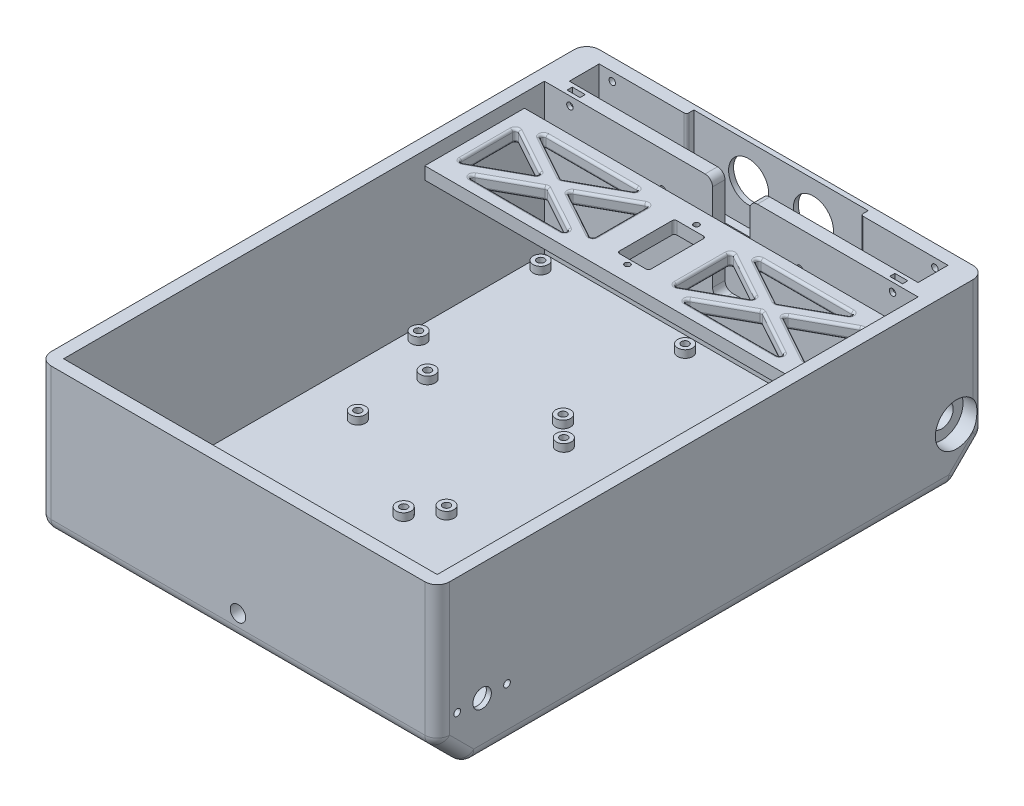
SolidWorks part; units mm, degrees
ref_plane "Front Plane" through (0, 0, 0) normal (0, 0, 1) x (1, 0, 0)
ref_plane "Top Plane" through (0, 0, 0) normal (0, 1, 0) x (1, 0, 0)
ref_plane "Right Plane" through (0, 0, 0) normal (1, 0, 0) x (0, 0, -1)
sketch "Main Body" plane through (0, 0, 0) normal (0, 1, 0) x (1, 0, 0)
  line L0 (-75, 110) -> (75, 110)
  line L1 (-75, -105) -> (75, -105)
  line L2 (-75, -105) -> (-75, 105)
  line L3 (-75, 105) -> (75, 105)
  line L4 (75, -105) -> (75, 105)
  line L5 (-75, -105) -> (75, 105) construction
  line L6 (-75, 105) -> (75, -105) construction
  line L7 (80, -105) -> (80, 105)
  line L8 (-75, -110) -> (75, -110)
  line L9 (-80, -105) -> (-80, 105)
  line L10 (-80, -110) -> (80, -110) construction
  line L11 (-80, -110) -> (-80, 110) construction
  line L12 (80, -110) -> (80, 110) construction
  line L13 (-80, 110) -> (80, 110) construction
  arc A0 (-75, -110) -> (-80, -105) centre (-75, -105) cw
  arc A1 (80, -105) -> (75, -110) centre (75, -105) cw
  arc A2 (75, 110) -> (80, 105) centre (75, 105) cw
  arc A3 (-75, 110) -> (-80, 105) centre (-75, 105) ccw
  point P0 (0, 0)
  dimension "D4" = 5
  dimension "D1" = 75
  dimension "D2" = 210
  dimension "D3" = 5
extrude "Boss-Extrude1" add sketch "Main Body" along normal blind 8 contours L1 L4 L3 L2 | L9 L8 L7 L0 L4 L1 L2 L3 region at (0, 0, -107.2797) region at (0, 0, 0)
extrude "Boss-Extrude3" add sketch "Main Body<4>" along normal blind 60 from surface starting at face at (0, 8, 0)
sketch "Main Body<4>" plane through (0, 0, 0) normal (0, 1, 0) x (1, 0, 0) same geometry as "Main Body"
sketch "Sketch1" plane through (75, 0, 0) normal (-1, 0, 0) x (0, 0, 1)
  line L0 (105, 68) -> (105, 8) construction
  line L1 (-105, 8) -> (105, 8) construction
  line L2 (79, 15.5) -> (105, 15.5)
  line L3 (79, 8) -> (105, 8)
  line L4 (79, 8) -> (79, 34)
  line L5 (79, 34) -> (105, 34)
  line L6 (105, 8) -> (105, 34)
  line L7 (79, 8) -> (105, 34) construction
  line L8 (79, 34) -> (105, 8) construction
  circle A0 centre (92, 21) radius 13
  line M2 (-105, 8) -> (105, 8)
  line M3 (105, 8) -> (105, 68)
  dimension "D1" = 26
  dimension "D2" = 7.5
extrude "Boss-Extrude4" add sketch "Sketch1" along normal up to surface (150 mm away) contours A0 L4 M2 | A0 L3 M3 region at (75, 10.5201, 82.0674) region at (75, 10.5201, 101.9326) up to face at (-75, 38, 0)
sketch "Sketch2" plane through (0, 0, 0) normal (1, 0, 0) x (0, 0, -1)
  line L0 (-105, 68) -> (-105, 15.5) construction
  line L1 (-105, 8) -> (-79, 8)
  line L2 (-105, 8) -> (-105, 15.5)
  line L3 (-105, 15.5) -> (-79, 15.5)
  line L4 (-79, 8) -> (-79, 15.5)
  line L5 (105, 8) -> (-79, 8) construction
  line L6 (-79, 8) -> (-79, 15.5) construction
  line L7 (-79, 15.5) -> (-80.2208, 15.5) construction
extrude "Cut-Extrude1" cut sketch "Sketch2" against normal mid plane 12
sketch "Sketch3" plane through (0, 8, 0) normal (0, 1, 0) x (1, 0, 0)
  line L0 (75, -105) -> (-75, -105) construction
  line L1 (-4, -79) -> (-11, -79)
  line L2 (-4, -79) -> (-4, -105)
  line L3 (-4, -105) -> (-11, -105)
  line L4 (-11, -79) -> (-11, -105)
  line L5 (0, 0) -> (0, -105) construction
  line L6 (-75, -79) -> (-6, -79) construction
  line L7 (11, -79) -> (11, -105)
  line L8 (4, -105) -> (11, -105)
  line L9 (4, -79) -> (4, -105)
  line L10 (4, -79) -> (11, -79)
  line L11 (-6, -103.7792) -> (-6, -92) construction
  dimension "D1" = 5
  dimension "D2" = 4
extrude "Boss-Extrude5" add sketch "Sketch3" along normal blind 20
sketch "Sketch4" plane through (0, 8, 0) normal (0, 1, 0) x (1, 0, 0)
  line L0 (-75, -105) -> (-75, 105) construction
  line L1 (-75, 93) -> (75, 93)
  line L2 (-75, 93) -> (-75, 88)
  line L3 (-75, 88) -> (75, 88)
  line L4 (75, 93) -> (75, 88)
  line L5 (75, 105) -> (75, -105) construction
  line L6 (-75, 105) -> (75, 105) construction
  dimension "D1" = 17
  dimension "D2" = 5
extrude "Boss-Extrude6" add sketch "Sketch4" along normal up to surface (60 mm away) up to face at (0, 68, 0)
sketch "Sketch5" plane through (80, 0, 0) normal (1, 0, 0) x (0, 0, -1)
  circle A0 centre (-92, 21) radius 3.5 construction
  circle A1 centre (-92, 21) radius 3.5
  circle A2 centre (-92, 21) radius 3.7
  dimension "D1" = 0.2
extrude "Cut-Extrude4" cut sketch "Sketch5" against normal up to next contours A1 | A2 A1 region at (80, 21, 92) region at (80, 21, 95.5953)
sketch "Sketch6" plane through (-75, 0, 0) normal (1, 0, 0) x (0, 0, -1)
  circle A0 centre (-92, 21) radius 13
  dimension "D1" = 26
extrude "Cut-Extrude5" cut sketch "Sketch6" against normal offset from surface (3 mm away) 2 up to face at (-80, 34, 0)
mirror "Mirror1" about plane through (0, 0, 0) normal (1, 0, 0) of "Cut-Extrude4"
sketch "Sketch8" plane through (75, 0, 0) normal (-1, 0, 0) x (0, 0, 1)
  circle A0 centre (92, 21) radius 13
  dimension "D1" = 26
extrude "Cut-Extrude6" cut sketch "Sketch8" against normal offset from surface (3 mm away) 2 up to face at (80, 21, 88.3)
sketch "Sketch10" plane through (80, 0, 0) normal (1, 0, 0) x (0, 0, -1)
  circle A1 centre (-82, 21) radius 1.25
  circle A2 centre (-82, 21) radius 1.25
  circle A3 centre (-102, 21) radius 1.25
  circle A4 centre (-102, 21) radius 1.25
  circle A5 centre (-92, 21) radius 12.5
  circle A6 centre (-92, 21) radius 12.5
  circle A63 centre (-102, 21) radius 1.35
  circle A64 centre (-82, 21) radius 1.35
  dimension "D1" = 0
  dimension "D2" = 0
  dimension "D3" = 0
  dimension "D4" = 0.1
  dimension "D5" = 0.1
extrude "Cut-Extrude7" cut sketch "Sketch10" against normal up to next contours A2 | A64 A2 | A4 | A63 A4 region at (80, 21, 82) region at (80, 21, 102) region at (80, 21, 103.3118) region at (80, 21, 83.3118)
mirror "Mirror3" about plane through (0, 0, 0) normal (1, 0, 0) of "Cut-Extrude7"
sketch "Sketch11" plane through (80, 0, 0) normal (1, 0, 0) x (0, 0, -1)
  circle A0 centre (98.5, 21) radius 4.5 construction
  circle A1 centre (98.5, 21) radius 4.5
  circle A3 centre (98.5, 21) radius 4.6
  dimension "D1" = 0.1
extrude "Cut-Extrude10" cut sketch "Sketch11" against normal through all contours A1 | A3 A1 region at (80, 21, -98.5) region at (80, 21, -93.913)
sketch "Sketch12" plane through (-75, 0, 0) normal (1, 0, 0) x (0, 0, -1)
  line L0 (93, 8) -> (105, 8) construction
  line L1 (93, 68) -> (105, 68)
  line L2 (93, 68) -> (93, 8)
  line L3 (93, 8) -> (105, 8)
  line L4 (105, 68) -> (105, 8)
  line L6 (93, 68) -> (93, 8) construction
  line L7 (93, 68) -> (105, 68) construction
  circle A2 centre (98.5, 21) radius 4.6 construction
  circle A3 centre (98.5, 21) radius 4.6
extrude "Boss-Extrude7" add sketch "Sketch12" along normal blind 5
sketch "Sketch13" plane through (-80, 0, 0) normal (-1, 0, 0) x (0, 0, 1)
  circle A0 centre (-98.5, 21) radius 8.55
  circle A2 centre (-98.5, 21) radius 4.6 construction
  dimension "D1" = 17.1
extrude "Cut-Extrude11" cut sketch "Sketch13" against normal blind 6
mirror "Mirror4" about plane through (0, 0, 0) normal (1, 0, 0) of "Boss-Extrude7", "Cut-Extrude11"
sketch "Sketch14" plane through (0, 8, 0) normal (0, 1, 0) x (1, 0, 0)
  line L0 (-4, -105) -> (-4, -79) construction
  line L1 (-4, -95) -> (4, -95)
  line L2 (-4, -95) -> (-4, -105)
  line L3 (-4, -105) -> (4, -105)
  line L4 (4, -95) -> (4, -105)
  dimension "D1" = 10
extrude "Boss-Extrude9" add sketch "Sketch14" along normal blind 5
sketch "Sketch15" plane through (0, 0, 110) normal (0, 0, 1) x (1, 0, 0)
  arc A0 (-3, 19.5) -> (3, 19.5) centre (0, 19.5) ccw construction
  arc A1 (-3, 19.5) -> (3, 19.5) centre (0, 19.5) ccw
  arc A2 (3, 19.5) -> (-3, 19.5) centre (0, 19.5) ccw construction
  arc A3 (3, 19.5) -> (-3, 19.5) centre (0, 19.5) ccw
  arc A4 (3.1, 19.5) -> (-3.1, 19.5) centre (0, 19.5) ccw
  arc A5 (-3.1, 19.5) -> (3.1, 19.5) centre (0, 19.5) ccw
  dimension "D1" = 0.1
extrude "Cut-Extrude12" cut sketch "Sketch15" against normal up to next contours A1 A3 | A4 A5 A3 A1 region at (0, 19.5, 110) region at (0, 16.4877, 110)
sketch "Sketch16" plane through (0, 0, 0) normal (0, -1, 0) x (1, 0, 0)
  circle A0 centre (-12.5, -82) radius 1.475 construction
  circle A1 centre (-70.5, -82) radius 1.475 construction
  circle A2 centre (-70.5, -33) radius 1.475 construction
  circle A3 centre (-12.5, -33) radius 1.475 construction
  circle A4 centre (-4.2, -25) radius 1.475 construction
  circle A5 centre (-55, -21.12) radius 1.475 construction
  circle A6 centre (-55, 6.88) radius 1.475 construction
  circle A7 centre (-4.2, 22.08) radius 1.475 construction
  circle A8 centre (-12.3, 31.18) radius 1.475 construction
  circle A9 centre (24.2, 31.18) radius 1.475 construction
  circle A10 centre (37.8459, 24.117) radius 1.475 construction
  circle A11 centre (59.5541, 24.117) radius 1.475 construction
  circle A12 centre (59.5541, 68.243) radius 1.475 construction
  circle A13 centre (37.8459, 68.243) radius 1.475 construction
  circle A14 centre (24.2, 67.68) radius 1.475 construction
  circle A15 centre (-12.3, 67.68) radius 1.475 construction
  circle A16 centre (-12.5, -82) radius 1.475
  circle A17 centre (-70.5, -82) radius 1.475
  circle A18 centre (-70.5, -33) radius 1.475
  circle A19 centre (-12.5, -33) radius 1.475
  circle A20 centre (-4.2, -25) radius 1.475
  circle A21 centre (-55, -21.12) radius 1.475
  circle A22 centre (-55, 6.88) radius 1.475
  circle A23 centre (-4.2, 22.08) radius 1.475
  circle A24 centre (-12.3, 31.18) radius 1.475
  circle A25 centre (24.2, 31.18) radius 1.475
  circle A26 centre (37.8459, 24.117) radius 1.475
  circle A27 centre (59.5541, 24.117) radius 1.475
  circle A28 centre (59.5541, 68.243) radius 1.475
  circle A29 centre (37.8459, 68.243) radius 1.475
  circle A30 centre (24.2, 67.68) radius 1.475
  circle A31 centre (-12.3, 67.68) radius 1.475
extrude "Cut-Extrude13" cut sketch "Sketch16" against normal up to next
sketch "Sketch17" plane through (0, 8, 0) normal (0, 1, 0) x (1, 0, 0)
  line L0 (0, 88) -> (0, -110) construction
  line L1 (-75, 88) -> (75, 88) construction
  line L2 (75, -110) -> (-75, -110) construction
  line L3 (-75, 4.5) -> (75, 4.5) construction
  line L7 (-75, -79) -> (-75, 88) construction
  line L8 (75, 88) -> (75, -79) construction
  circle A0 centre (-70.5, 82) radius 3
  circle A1 centre (-12.5, 82) radius 3
  circle A2 centre (-12.3, -67.68) radius 1.475
  circle A3 centre (-12.3, -67.68) radius 1.475
  circle A4 centre (24.2, -67.68) radius 1.475
  circle A5 centre (24.2, -67.68) radius 1.475
  circle A6 centre (37.8459, -68.243) radius 1.475
  circle A7 centre (37.8459, -68.243) radius 1.475
  circle A8 centre (59.5541, -68.243) radius 1.475
  circle A9 centre (59.5541, -68.243) radius 1.475
  circle A10 centre (59.5541, -24.117) radius 1.475
  circle A11 centre (59.5541, -24.117) radius 1.475
  circle A12 centre (37.8459, -24.117) radius 1.475
  circle A13 centre (37.8459, -24.117) radius 1.475
  circle A14 centre (24.2, -31.18) radius 1.475
  circle A15 centre (24.2, -31.18) radius 1.475
  circle A16 centre (-12.3, -31.18) radius 1.475
  circle A17 centre (-12.3, -31.18) radius 1.475
  circle A18 centre (-4.2, -22.08) radius 1.475
  circle A19 centre (-4.2, -22.08) radius 1.475
  circle A20 centre (-55, -6.88) radius 1.475
  circle A21 centre (-55, -6.88) radius 1.475
  circle A22 centre (-55, 21.12) radius 1.475
  circle A23 centre (-55, 21.12) radius 1.475
  circle A24 centre (-4.2, 25) radius 1.475
  circle A25 centre (-4.2, 25) radius 1.475
  circle A26 centre (-12.5, 33) radius 1.475
  circle A27 centre (-12.5, 33) radius 1.475
  circle A28 centre (-70.5, 33) radius 1.475
  circle A29 centre (-70.5, 33) radius 1.475
  circle A30 centre (-70.5, 82) radius 1.475
  circle A31 centre (-70.5, 82) radius 1.475
  circle A32 centre (-12.5, 82) radius 1.475
  circle A33 centre (-12.5, 82) radius 1.475
  circle A34 centre (-70.5, 33) radius 3
  circle A35 centre (-55, 21.12) radius 3
  circle A36 centre (-12.5, 33) radius 3
  circle A37 centre (-4.2, 25) radius 3
  circle A38 centre (-55, -6.88) radius 3
  circle A39 centre (-4.2, -22.08) radius 3
  circle A40 centre (-12.3, -31.18) radius 3
  circle A41 centre (24.2, -31.18) radius 3
  circle A42 centre (37.8459, -24.117) radius 3
  circle A43 centre (59.5541, -24.117) radius 3
  circle A44 centre (-12.3, -67.68) radius 3
  circle A45 centre (24.2, -67.68) radius 3
  circle A46 centre (37.8459, -68.243) radius 3
  circle A47 centre (59.5541, -68.243) radius 3
  dimension "D1" = 6
  dimension "D2" = 0
  dimension "D3" = 0
  dimension "D4" = 0
  dimension "D5" = 0
  dimension "D6" = 0
  dimension "D7" = 0
  dimension "D8" = 0
  dimension "D9" = 0
  dimension "D10" = 0
  dimension "D11" = 0
  dimension "D12" = 0
  dimension "D13" = 0
  dimension "D14" = 0
  dimension "D15" = 0
  dimension "D16" = 0
  dimension "D17" = 0
extrude "Boss-Extrude10" add sketch "Sketch17" along normal blind 3
sketch "Sketch18" plane through (75, 0, 0) normal (-1, 0, 0) x (0, 0, 1)
  line L1 (-80, 62.6) -> (-40, 62.6)
  line L2 (-80, 62.6) -> (-80, 57.6)
  line L3 (-80, 57.6) -> (-40, 57.6)
  line L4 (-40, 62.6) -> (-40, 57.6)
  line L5 (-88, 68) -> (105, 68) construction
  dimension "D1" = 5
  dimension "D2" = 30
  dimension "D3" = 40
  dimension "D4" = 5.4
extrude "Boss-Extrude11" add sketch "Sketch18" along normal up to next
sketch "Sketch19" plane through (0, 68, 0) normal (0, 1, 0) x (1, 0, 0)
  line L1 (-6.3, 71.5) -> (6.3, 71.5)
  line L2 (-6.3, 71.5) -> (-6.3, 48.5)
  line L3 (-6.3, 48.5) -> (6.3, 48.5)
  line L4 (6.3, 71.5) -> (6.3, 48.5)
  line L12 (-75, 80) -> (-75, 40)
  line L13 (-75, 40) -> (75, 40)
  line L14 (75, 40) -> (75, 80)
  line L15 (75, 80) -> (-75, 80)
  line L16 (-75, 80) -> (-75, 40)
  line L17 (-75, 40) -> (75, 40)
  line L18 (75, 40) -> (75, 80)
  line L19 (75, 80) -> (-75, 80)
  point P4 (0, 71.5)
  point P8 (0, 80)
  point P12 (6.3, 60)
  point P13 (75, 60)
  dimension "D1" = 23
  dimension "D2" = 12.6
  dimension "D3" = 0
extrude "Cut-Extrude14" cut sketch "Sketch19" against normal up to next contours L4 L1 L2 L3 region at (0, 68, -60)
sketch "Sketch21" plane through (0, 0, -110) normal (0, 0, -1) x (-1, 0, 0)
  circle A1 centre (-64.75, 64.5) radius 1.3
  circle A2 centre (-64.75, 64.5) radius 1.3
  circle A3 centre (64.75, 64.5) radius 1.3
  circle A4 centre (64.75, 64.5) radius 1.3
  dimension "D1" = 0
  dimension "D2" = 0
extrude "Cut-Extrude16" cut sketch "Sketch21" against normal up to surface (22 mm away) up to face at (0, 38, -88)
ref_plane "Plane1" through (0, 0, -90.5) normal (0, 0, -1) x (-1, 0, 0)
sketch "Sketch22" plane through (0, 0, -90.5) normal (0, 0, -1) x (-1, 0, 0)
  line L0 (-67.35, 66.0011) -> (-67.35, 68)
  line L1 (-62.15, 66.0011) -> (-64.75, 67.5022)
  line L2 (-64.75, 67.5022) -> (-67.35, 66.0011)
  line L3 (-67.35, 66.0011) -> (-67.35, 62.9989)
  line L4 (-67.35, 62.9989) -> (-64.75, 61.4978)
  line L5 (-64.75, 61.4978) -> (-62.15, 62.9989)
  line L6 (-62.15, 62.9989) -> (-62.15, 66.0011)
  line L7 (-67.35, 68) -> (-62.15, 68)
  line L8 (-62.15, 68) -> (-62.15, 66.0011)
  line L9 (70, 68) -> (-70, 68) construction
  line L10 (0, 0) -> (0, 68) construction
  line L11 (75, 68) -> (-75, 68) construction
  line L12 (64.75, 61.4978) -> (62.15, 62.9989)
  line L13 (67.35, 62.9989) -> (64.75, 61.4978)
  line L14 (64.75, 67.5022) -> (67.35, 66.0011)
  line L15 (67.35, 66.0011) -> (67.35, 62.9989)
  line L16 (67.35, 66.0011) -> (67.35, 68)
  line L17 (62.15, 62.9989) -> (62.15, 66.0011)
  line L18 (62.15, 68) -> (62.15, 66.0011)
  line L19 (67.35, 68) -> (62.15, 68)
  line L20 (62.15, 66.0011) -> (64.75, 67.5022)
  circle A0 centre (-64.75, 64.5) radius 2.6 construction
  dimension "D1" = 5.2
extrude "Cut-Extrude17" cut sketch "Sketch22" against normal mid plane 2.1 contours L20 L17 L12 L13 L15 L14 | L18 L20 L14 L16 L19 | L5 L6 L1 L2 L3 L4 | L8 L7 L0 L2 L1 region at (67.2943, 67.0006, -90.5) region at (64.75, 64.5, -90.5) region at (-64.75, 64.5, -90.5) region at (-62.2057, 67.0006, -90.5)
sketch "Sketch23" plane through (0, 0, -110) normal (0, 0, -1) x (-1, 0, 0)
  circle A0 centre (64.75, 64.5) radius 2.5
  circle A1 centre (-64.75, 64.5) radius 2.5
  dimension "D1" = 5
  dimension "D2" = 5
extrude "Cut-Extrude18" cut sketch "Sketch23" against normal mid plane 2.5
sketch "Sketch24" plane through (0, 62.6, 0) normal (0, 1, 0) x (1, 0, 0)
  circle A0 centre (0, 46.35) radius 1.1002
  arc A1 (0.4, 45.4333) -> (-0.4, 45.4333) centre (0, 46.35) ccw construction
  circle A2 centre (0, 74.05) radius 1.1002
  arc A3 (-0.4, 74.9667) -> (0, 73.0498) centre (0, 74.05) ccw construction
  point P5 (0.4, 45.4333)
  dimension "D1" = 0.1
extrude "Cut-Extrude19" cut sketch "Sketch24" against normal up to next
sketch "Sketch25" plane through (0, 62.6, 0) normal (0, 1, 0) x (1, 0, 0)
  line L0 (6.3, 71.5) -> (6.3, 48.5) construction
  line L1 (-11.3, 80) -> (11.3, 80)
  line L2 (-11.3, 80) -> (-11.3, 40)
  line L3 (-11.3, 40) -> (11.3, 40)
  line L4 (-75, 80) -> (-75, 40)
  line L5 (-75, 40) -> (75, 40)
  line L6 (75, 40) -> (75, 80)
  line L7 (75, 80) -> (-75, 80)
  line L8 (-75, 80) -> (-75, 40)
  line L9 (-75, 40) -> (75, 40)
  line L10 (75, 40) -> (75, 80)
  line L11 (75, 80) -> (-75, 80)
  line L12 (11.3, 80) -> (11.3, 40)
  line L13 (-11.3, 80) -> (11.3, 40) construction
  line L14 (-11.3, 40) -> (11.3, 80) construction
  line L15 (0, 80) -> (0, 40) construction
  line L16 (70, 75) -> (70, 45)
  line L17 (-70, 75) -> (-16.3, 75)
  line L18 (-70, 75) -> (-70, 45)
  line L19 (-70, 45) -> (-16.3, 45)
  line L20 (-16.3, 75) -> (-16.3, 45)
  line L21 (-70, 75) -> (-16.3, 45) construction
  line L22 (-70, 45) -> (-16.3, 75) construction
  line L23 (70, 75) -> (16.3, 45) construction
  line L24 (70, 45) -> (16.3, 75) construction
  line L25 (70, 75) -> (16.3, 75)
  line L26 (16.3, 75) -> (16.3, 45)
  line L27 (70, 45) -> (16.3, 45)
  line L28 (-75, 60) -> (-11.3, 60) construction
  line L29 (75, 60) -> (11.3, 60) construction
  line L30 (-70, 71.9362) -> (-48.3314, 60)
  line L31 (-16.3, 71.9362) -> (-37.9686, 60)
  line L32 (70, 71.9362) -> (48.3314, 60)
  line L33 (-48.3314, 60) -> (-70, 48.0638)
  line L34 (48.3314, 60) -> (70, 48.0638)
  line L35 (-65.199, 45) -> (-43.15, 57.1458)
  line L36 (65.199, 45) -> (43.15, 57.1458)
  line L37 (-43.15, 57.1458) -> (-21.101, 45)
  line L38 (43.15, 57.1458) -> (21.101, 45)
  line L39 (16.3, 71.9362) -> (37.9686, 60)
  line L40 (-37.9686, 60) -> (-16.3, 48.0638)
  line L41 (37.9686, 60) -> (16.3, 48.0638)
  line L42 (-65.199, 75) -> (-43.15, 62.8542)
  line L43 (65.199, 75) -> (43.15, 62.8542)
  line L44 (-43.15, 62.8542) -> (-21.101, 75)
  line L45 (43.15, 62.8542) -> (21.101, 75)
  line L46 (-75, 40) -> (-75, 80) construction
  line L47 (-75, 40) -> (75, 40) construction
  point P2 (0, 60)
  point P9 (-43.15, 60)
  point P10 (75, 60)
  point P24 (43.15, 60)
  point P62 (-54.1745, 68.9271)
  dimension "D2" = 5
  dimension "D3" = 5
  dimension "D4" = 5
  dimension "D5" = 5
  dimension "D6" = 26.6686
  dimension "D1" = 0
extrude "Cut-Extrude21" cut sketch "Sketch25" against normal up to next contours L37 L35 L19 | L33 L30 L18 | L42 L44 L17 | L31 L40 L20 | L41 L39 L26 | L45 L43 L25 | L36 L38 L27 | L32 L34 L16 region at (62.7771, 62.6, -60) region at (43.15, 62.6, -70.9514) region at (43.15, 62.6, -49.0486) region at (23.5229, 62.6, -60) region at (-43.15, 62.6, -70.9514) region at (-62.7771, 62.6, -60) region at (-23.5229, 62.6, -60) region at (-43.15, 62.6, -49.0486)
sketch "Sketch26" plane through (-80, 0, 0) normal (-1, 0, 0) x (0, 0, 1)
  line L0 (-110, 12.58) -> (-97.42, 0)
  line L1 (-110, 68) -> (-110, 0) construction
  line L2 (105, 0) -> (-105, 0) construction
  line L3 (-97.42, 0) -> (-92.42, 0)
  line L4 (-92.42, 0) -> (-110, 17.58)
  line L5 (-110, 17.58) -> (-110, 12.58)
  line L6 (-110, 12.58) -> (-110, 0)
  line L7 (-110, 0) -> (-97.42, 0)
  circle A1 centre (-98.5, 21) radius 8.55 construction
  line M5 (-105, 15.4455) -> (-105, 0)
  line M6 (-105, 0) -> (105, 0)
  dimension "D1" = 2
  dimension "D2" = 5
  dimension "D3" = 45
extrude "Cut-Extrude22" cut sketch "Sketch26" against normal up to next contours L6 L7 L0 M5 | L0 M5 M6 region at (-80, 5.1434, -107.7067) region at (-80, 2.5267, -102.4733)
mirror "Mirror5" about plane through (0, 0, 0) normal (0, 0, 1) of "Cut-Extrude22"
fillet "Fillet1" radius 5 14 edges at (80, 3.79, -101.21) (78.5355, 11.1156, -108.5355) (-80, 3.79, -101.21) (-78.5355, 11.1156, -108.5355) (80, 3.79, 101.21) (78.5355, 11.1156, 108.5355) (-80, 3.79, 101.21) (-78.5355, 11.1156, 108.5355) (0, 0, -97.42) (0, 12.58, -110) (0, 0, 97.42) (0, 12.58, 110) (-80, 0, 0) (80, 0, 0)
fillet "Fillet2" radius 1 76 edges at (-32.1255, 57.6, -51.0729) (-32.1255, 62.6, -51.0729) (-21.101, 60.1, -45) (-43.15, 62.6, -45) (-43.15, 57.6, -45) (-54.1745, 57.6, -51.0729) (-65.199, 60.1, -45) (-54.1745, 62.6, -51.0729) (-43.15, 60.1, -57.1458) (32.1255, 57.6, -68.9271) (32.1255, 62.6, -68.9271) (21.101, 60.1, -75) (43.15, 62.6, -75) (43.15, 57.6, -75) (54.1745, 57.6, -68.9271) (65.199, 60.1, -75) (54.1745, 62.6, -68.9271) (43.15, 60.1, -62.8542) (54.1745, 62.6, -51.0729) (54.1745, 57.6, -51.0729) (43.15, 57.6, -45) (65.199, 60.1, -45) (43.15, 62.6, -45) (21.101, 60.1, -45) (32.1255, 62.6, -51.0729) (43.15, 60.1, -57.1458) (32.1255, 57.6, -51.0729) (59.1657, 62.6, -65.9681) (59.1657, 57.6, -65.9681) (70, 57.6, -60) (70, 60.1, -71.9362) (70, 62.6, -60) (70, 60.1, -48.0638) (59.1657, 62.6, -54.0319) (48.3314, 60.1, -60) (59.1657, 57.6, -54.0319) (-54.1745, 62.6, -68.9271) (-54.1745, 57.6, -68.9271) (-43.15, 57.6, -75) (-65.199, 60.1, -75) (-43.15, 62.6, -75) (-21.101, 60.1, -75) (-32.1255, 62.6, -68.9271) (-43.15, 60.1, -62.8542) (-32.1255, 57.6, -68.9271) (-59.1657, 57.6, -54.0319) (-59.1657, 62.6, -54.0319) (-70, 60.1, -48.0638) (-70, 62.6, -60) (-70, 57.6, -60) (-59.1657, 57.6, -65.9681) (-70, 60.1, -71.9362) (-59.1657, 62.6, -65.9681) (-48.3314, 60.1, -60) (-27.1343, 62.6, -65.9681) (-27.1343, 57.6, -65.9681) (-16.3, 57.6, -60) (-16.3, 60.1, -71.9362) (-16.3, 62.6, -60) (-16.3, 60.1, -48.0638) (-27.1343, 62.6, -54.0319) (-37.9686, 60.1, -60) (-27.1343, 57.6, -54.0319) (27.1343, 57.6, -54.0319) (27.1343, 62.6, -54.0319) (16.3, 60.1, -48.0638) (16.3, 62.6, -60) (16.3, 57.6, -60) (27.1343, 57.6, -65.9681) (16.3, 60.1, -71.9362) (27.1343, 62.6, -65.9681) (37.9686, 60.1, -60) (6.3, 60.1, -48.5) (-6.3, 60.1, -48.5) (-6.3, 60.1, -71.5) (6.3, 60.1, -71.5)
sketch "Sketch33" plane through (0, 0, -110) normal (0, 0, -1) x (-1, 0, 0)
  circle A0 centre (-13, 53.9999) radius 8.05
  circle A1 centre (13, 53.9999) radius 8.05
  circle A2 centre (-13, 53.9999) radius 7.3 construction
  circle A3 centre (13, 53.9999) radius 7.3 construction
  dimension "D1" = 16.1
extrude "Cut-Extrude27" cut sketch "Sketch33" against normal up to next
sketch "Sketch34" plane through (0, 0, -93) normal (0, 0, -1) x (-1, 0, 0)
  circle A0 centre (27.525, 54) radius 1.3 construction
  circle A1 centre (27.525, 54) radius 1.3
  circle A2 centre (-27.525, 54) radius 1.3 construction
  circle A3 centre (-27.525, 54) radius 1.3
extrude "Cut-Extrude28" cut sketch "Sketch34" against normal up to next
sketch "Sketch35" plane through (0, 68, 0) normal (0, 1, 0) x (1, 0, 0)
  line L0 (70, 93) -> (-70, 93) construction
  line L1 (-7.5, 93) -> (7.5, 93)
  line L2 (-7.5, 93) -> (-7.5, 88)
  line L3 (-7.5, 88) -> (7.5, 88)
  line L4 (7.5, 93) -> (7.5, 88)
  line L5 (-7.5, 93) -> (7.5, 88) construction
  line L6 (-7.5, 88) -> (7.5, 93) construction
  line L7 (-75, 88) -> (75, 88) construction
  point P0 (0, 90.5)
  dimension "D1" = 15
extrude "Cut-Extrude29" cut sketch "Sketch35" against normal offset from surface (41 mm away) 19 up to face at (37.8459, 8, 71.243)
fillet "Fillet4" radius 3 9 edges at (0, 8, 95) (-7.5, 28, 79) (-7.5, 28, 105) (7.5, 28, 105) (7.5, 28, 79) (-7.5, 68, -90.5) (7.5, 68, -90.5) (-7.5, 27, -90.5) (7.5, 27, -90.5)
fillet "Fillet5" radius 1 1 edges at (0, 13, 95)
sketch "Sketch36" plane through (0, 68, 0) normal (0, 1, 0) x (1, 0, 0)
  line L0 (-70, 105) -> (70, 105) construction
  line L1 (-35, 108) -> (35, 108)
  line L2 (-35, 108) -> (-35, 105)
  line L3 (-35, 105) -> (35, 105)
  line L4 (35, 108) -> (35, 105)
  line L5 (-75, 110) -> (75, 110) construction
  point P6 (0, 108)
  dimension "D1" = 70
  dimension "D2" = 2
extrude "Cut-Extrude30" cut sketch "Sketch36" against normal blind 30
fillet "Fillet6" radius 1 2 edges at (35, 53, -105) (-35, 53, -105)
